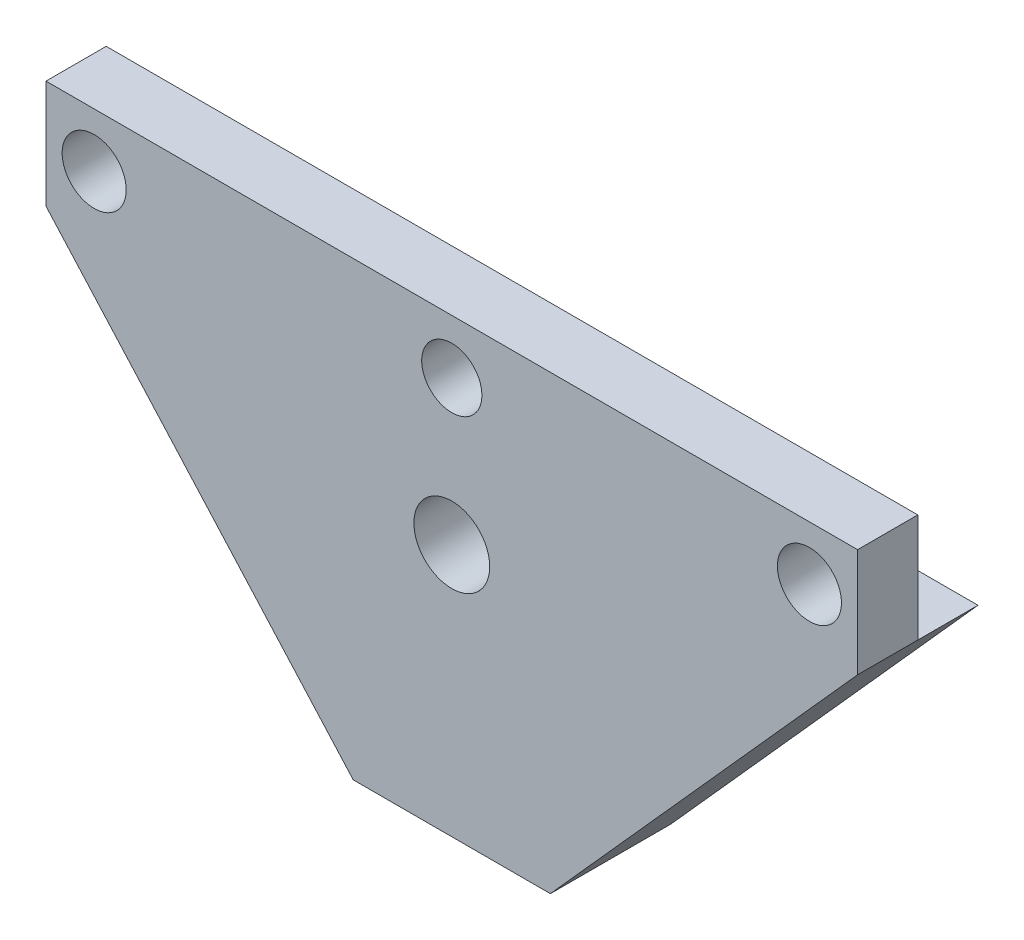
SolidWorks part; units mm, degrees
material "6061 Alloy"
ref_plane "Front Plane" through (0, 0, 0) normal (0, 0, 1) x (1, 0, 0)
ref_plane "Top Plane" through (0, 0, 0) normal (0, 1, 0) x (1, 0, 0)
ref_plane "Right Plane" through (0, 0, 0) normal (1, 0, 0) x (0, 0, -1)
sketch "Sketch1" plane through (0, 0, 0) normal (0, 0, 1) x (1, 0, 0)
  line L0 (-42.8001, -5.715) -> (-10.3954, -41.91)
  line L2 (-42.8001, -5.715) -> (-42.8001, 5.715)
  line L3 (-42.8001, 5.715) -> (42.8001, 5.715)
  line L4 (42.8001, -5.715) -> (42.8001, 5.715)
  line L5 (-10.3954, -41.91) -> (10.3954, -41.91)
  line L6 (10.3954, -41.91) -> (42.8001, -5.715)
  line L7 (0, 5.715) -> (0, -41.91) construction
  circle A0 centre (0, 0) radius 48.26 construction
  circle A1 centre (0, 0) radius 3.175 construction
  dimension "D1" = 96.52
  dimension "D2" = 6.35
  dimension "D6" = 6.35
  dimension "D3" = 5.715
  dimension "D4" = 5.08
  dimension "D5" = 5.08
  dimension "D7" = 5.08
extrude "Boss-Extrude1" add sketch "Sketch1" against normal blind 12.7
sketch "Sketch2" plane through (0, 0, 0) normal (0, 0, 1) x (1, 0, 0)
  circle A0 centre (0, 0) radius 3.175
  dimension "D1" = 6.35
extrude "Cut-Extrude1" cut sketch "Sketch2" against normal through all
sketch "Sketch3" plane through (42.8001, 0, 0) normal (1, 0, 0) x (0, 0, -1)
  line L0 (12.7, -5.715) -> (0, -5.715) construction
  line L1 (12.7, 5.715) -> (6.35, 5.715)
  line L2 (12.7, 5.715) -> (12.7, -5.715)
  line L3 (12.7, -5.715) -> (6.35, -5.715)
  line L4 (6.35, 5.715) -> (6.35, -5.715)
  line L5 (0, -5.715) -> (0, 5.715) construction
  dimension "D1" = 6.35
extrude "Cut-Extrude2" cut sketch "Sketch3" against normal through all
sketch "Sketch4" plane through (0, 0, 0) normal (0, 0, 1) x (1, 0, 0)
  line L0 (0, 0) -> (0, -15.24) construction
  circle A0 centre (0, -15.24) radius 4
  dimension "D2" = 8
  dimension "D1" = 15.24
extrude "Cut-Extrude3" cut sketch "Sketch4" against normal through all
hole_wizard "1/4 Clearance Hole1" positions "Sketch6" profile "Sketch7" hole size "1/4" standard "ANSI Inch" end condition through all
sketch "Sketch6" plane through (0, 0, -6.35) normal (0, 0, -1) x (-1, 0, 0)
  line L0 (-37.7201, 0) -> (0, 0) construction
  line L1 (0, 0) -> (37.7201, 0) construction
  line L3 (-42.8001, 5.715) -> (-42.8001, -5.715) construction
  point P0 (-37.7201, 0)
  point P2 (37.7201, 0)
  dimension "D1" = 5.08
sketch "Sketch7" plane through (37.7201, 0, -6.35) normal (1, 0, 0) x (0, 1, 0)
  line L0 (0, 0) -> (0, 6.35)
  line L1 (0, 6.35) -> (3.3782, 6.35)
  line L2 (3.3782, 6.35) -> (3.3782, 0)
  line L5 (3.3782, 0) -> (0, 0)
  line L11 (0, -6.35) -> (0, 107.95) construction
  dimension "Thru Hole Dia." = 6.7564
  dimension "Thru Hole Depth" = 6.35
